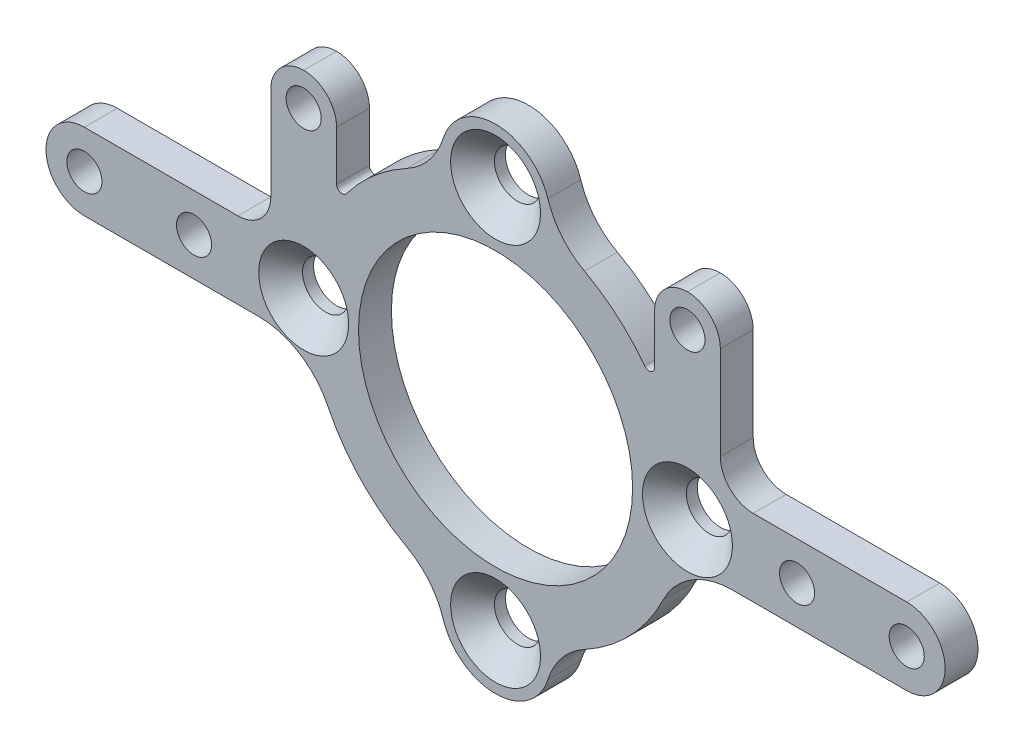
SolidWorks part; units mm, degrees
material "6061 合金"
ref_plane "正面" through (0, 0, 0) normal (0, 0, 1) x (1, 0, 0)
ref_plane "平面" through (0, 0, 0) normal (0, 1, 0) x (1, 0, 0)
ref_plane "右側面" through (0, 0, 0) normal (1, 0, 0) x (0, 0, -1)
sketch "ｽｹｯﾁ1" plane through (0, 0, 0) normal (0, 0, 1) x (1, 0, 0)
  line L0 (-41, 0) -> (41, 0) construction
  line L5 (-14.5, 37.2864) -> (-14.5, -33.9419) construction
  line L6 (14.5, 39.2615) -> (14.5, -48.2423) construction
  line L11 (-37.5, -3.5) -> (-16.6358, -3.5)
  line L12 (0, -22.5) -> (0, 24.5553) construction
  line L13 (-37.5, 3.5) -> (-20.5, 3.5)
  line L14 (37.5, -3.5) -> (16.6358, -3.5)
  line L15 (37.5, 3.5) -> (20.5, 3.5)
  line L16 (-14.5, 8.8741) -> (-14.5, 18)
  line L17 (-14.5, 18) -> (-20.5, 18)
  line L18 (-20.5, 18) -> (-20.5, 3.5)
  line L19 (14.5, 8.8741) -> (14.5, 18)
  line L20 (14.5, 18) -> (20.5, 18)
  line L21 (20.5, 18) -> (20.5, 3.5)
  line L22 (-17.5, 18) -> (-17.5, -3.5) construction
  line L23 (17.5, 18) -> (17.5, -3.5) construction
  circle A8 centre (0, 0) radius 12.5
  circle A17 centre (0, 17.5) radius 2.1
  circle A18 centre (-17.5, 0) radius 2.1
  circle A19 centre (0, -17.5) radius 2.1
  circle A20 centre (17.5, 0) radius 2.1
  circle A21 centre (-27.5, 0) radius 1.6
  circle A22 centre (-37.5, 0) radius 1.6
  circle A23 centre (27.5, 0) radius 1.6
  circle A24 centre (37.5, 0) radius 1.6
  arc A25 (-37.5, -3.5) -> (-37.5, 3.5) centre (-37.5, 0) cw
  arc A26 (37.5, 3.5) -> (37.5, -3.5) centre (37.5, 0) cw
  arc A27 (-16.6358, -3.5) -> (-4.8521, -16.2929) centre (0, 0) ccw
  arc A28 (-14.5, 8.8741) -> (-4.8521, 16.2929) centre (0, 0) cw
  arc A29 (4.8521, 16.2929) -> (14.5, 8.8741) centre (0, 0) cw
  arc A30 (4.8521, -16.2929) -> (16.6358, -3.5) centre (0, 0) ccw
  arc A31 (-4.8521, -16.2929) -> (4.8521, -16.2929) centre (0, -17.5) ccw
  arc A32 (-4.8521, 16.2929) -> (4.8521, 16.2929) centre (0, 17.5) cw
  circle A33 centre (-17.5, 15) radius 1.6
  circle A34 centre (17.5, 15) radius 1.6
  point P0 (0, 0)
  point P6 (0, 0)
  point P21 (0, 0)
  point P27 (0, 0)
  dimension "D3" = 17.5
  dimension "D1" = 17.5
  dimension "D5" = 25
  dimension "D11" = 10
  dimension "D12" = 10
  dimension "D13" = 29
  dimension "D14" = 3.5
  dimension "D15" = 17
  dimension "D16" = 5
  dimension "D17" = 6
  dimension "D18" = 18
  dimension "D2" = 17.5
  dimension "D4" = 17.5
  dimension "D7" = 10
  dimension "D8" = 10
  dimension "D9" = 4.2
  dimension "D10" = 3.2
  dimension "D21" = 3.2
  dimension "D22" = 3
  dimension "D6" = 14.5
  dimension "D19" = 6
  dimension "D20" = 18
extrude "ﾎﾞｽ - 押し出し1" add sketch "ｽｹｯﾁ1" along normal blind 3
fillet "ﾌｨﾚｯﾄ2" radius 7 6 edges at (-4.8521, 16.2929, 1.5) (4.8521, 16.2929, 1.5) (16.6358, -3.5, 1.5) (4.8521, -16.2929, 1.5) (-4.8521, -16.2929, 1.5) (-16.6358, -3.5, 1.5)
fillet "ﾌｨﾚｯﾄ3" radius 3 6 edges at (20.5, 18, 1.5) (14.5, 18, 1.5) (20.5, 3.5, 1.5) (-14.5, 18, 1.5) (-20.5, 18, 1.5) (-20.5, 3.5, 1.5)
fillet "ﾌｨﾚｯﾄ4" radius 0.5 2 edges at (14.5, 8.8741, 1.5) (-14.5, 8.8741, 1.5)
chamfer "面取り1" distance 2 angle 45 4 edges at (2.1, -17.5, 3) (-15.4, 0, 3) (19.6, 0, 3) (2.1, 17.5, 3)
